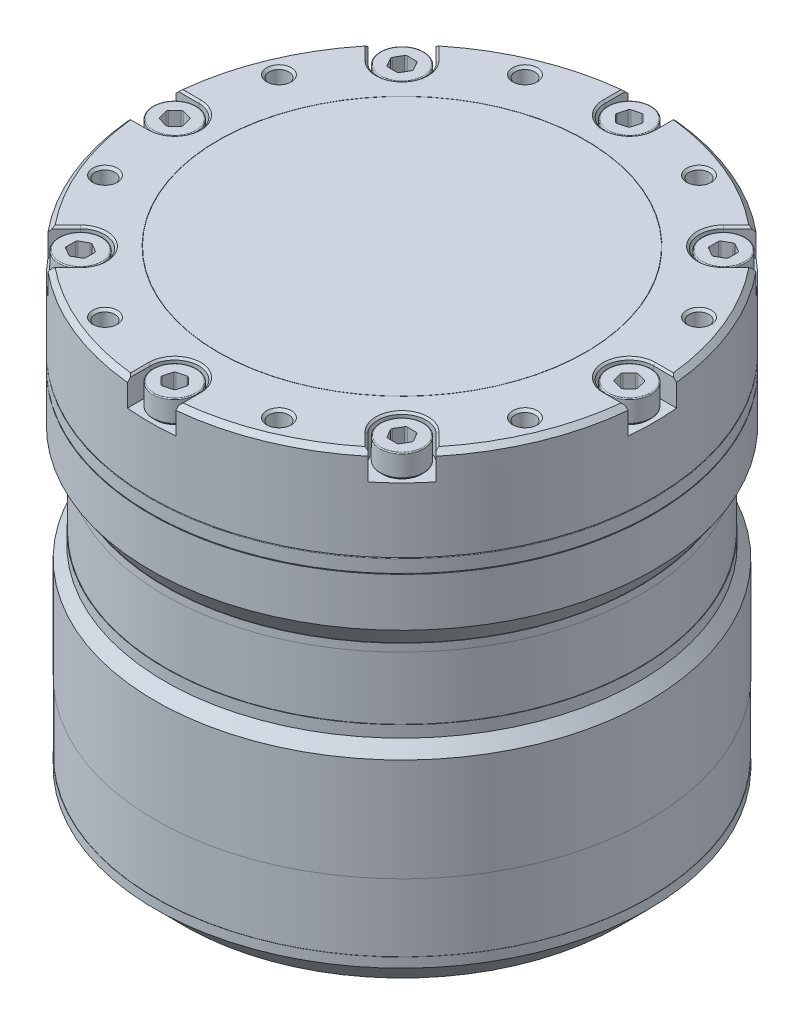
SolidWorks part; units mm, degrees
ref_plane "前视基准面" through (0, 0, 0) normal (0, 0, 1) x (1, 0, 0)
ref_plane "上视基准面" through (0, 0, 0) normal (0, 1, 0) x (1, 0, 0)
ref_plane "右视基准面" through (0, 0, 0) normal (1, 0, 0) x (0, 0, -1)
sketch "草图1" plane through (0, 0, 0) normal (0, 1, 0) x (1, 0, 0)
  circle A0 centre (0, 0) radius 26
  dimension "D1" = 52
extrude "凸台-拉伸1" add sketch "草图1" along normal blind 1.5
fillet "圆角1" radius 0.1 2 edges at (0, 0, 26) (0, 1.5, 26)
sketch "草图2" plane through (0, 1.5, 0) normal (0, 1, 0) x (1, 0, 0)
  circle A0 centre (0, 0) radius 26
  dimension "D1" = 52
extrude "凸台-拉伸2" add sketch "草图2" along normal blind 9.5
chamfer "倒角3" distance 0.5 angle 45 1 edges at (0, 11, 26)
sketch "草图4" plane through (0, 11, 0) normal (0, 1, 0) x (1, 0, 0)
  line L0 (0, 23.5) -> (0, 0) construction
  circle A0 centre (0, 23.5) radius 1.35
  dimension "D1" = 2.7
  dimension "D2" = 23.5
extrude "切除-拉伸1" cut sketch "草图4" against normal through all both and the other way through all
sketch "草图5" plane through (0, 11, 0) normal (0, 1, 0) x (1, 0, 0)
  line L0 (-2.5, 23.5) -> (-2.5, 26)
  line L1 (-2.5, 26) -> (2.5, 26)
  line L2 (2.5, 26) -> (2.5, 23.5)
  circle A0 centre (0, 23.5) radius 2.5 construction
  circle A1 centre (0, 0) radius 26 construction
  arc A2 (-2.5, 23.5) -> (2.5, 23.5) centre (0, 23.5) ccw
  dimension "D1" = 5
extrude "切除-拉伸2" cut sketch "草图5" against normal blind 2.8
chamfer "倒角1" distance 0.2 angle 45 3 edges at (-2.5, 11, -24.4386) (2.5, 11, -24.4386) (0, 11, -21)
sketch "草图6" plane through (0, 8.2, 0) normal (0, 1, 0) x (1, 0, 0)
  circle A0 centre (0, 23.5) radius 2
  dimension "D1" = 4
extrude "凸台-拉伸3" add sketch "草图6" along normal blind 0.5
sketch "草图7" plane through (0, 8.7, 0) normal (0, 1, 0) x (1, 0, 0)
  circle A0 centre (0, 23.5) radius 2.25
  dimension "D1" = 4.5
extrude "凸台-拉伸4" add sketch "草图7" along normal blind 2
chamfer "倒角2" distance 0.5 angle 45 1 edges at (0, 8.7, -21.5)
fillet "圆角2" radius 0.1 2 edges at (0, 10.7, -21.25) (0, 8.45, -21.25)
sketch "草图8" plane through (0, 10.7, 0) normal (0, 1, 0) x (1, 0, 0)
  line L1 (0.8425, 22.7904) -> (1.0865, 23.6814)
  line L2 (1.0358, 23.8748) -> (0.3862, 24.5316)
  line L3 (0.1933, 24.5844) -> (-0.7003, 24.3502)
  line L4 (-0.8425, 24.2096) -> (-1.0865, 23.3186)
  line L5 (-1.0358, 23.1252) -> (-0.3862, 22.4684)
  line L6 (-0.1933, 22.4156) -> (0.7003, 22.6498)
  circle A0 centre (0, 23.5) radius 1 construction
  arc A1 (-0.3862, 22.4684) -> (-0.1933, 22.4156) centre (-0.244, 22.609) ccw
  arc A2 (-1.0865, 23.3186) -> (-1.0358, 23.1252) centre (-0.8936, 23.2658) ccw
  arc A3 (-0.7003, 24.3502) -> (-0.8425, 24.2096) centre (-0.6496, 24.1568) ccw
  arc A4 (0.3862, 24.5316) -> (0.1933, 24.5844) centre (0.244, 24.391) ccw
  arc A5 (1.0865, 23.6814) -> (1.0358, 23.8748) centre (0.8936, 23.7342) ccw
  arc A6 (0.8425, 22.7904) -> (0.7003, 22.6498) centre (0.6496, 22.8432) cw
  dimension "D2" = 0.2
  dimension "D1" = 2
extrude "切除-拉伸3" cut sketch "草图8" against normal blind 1.8
sketch "草图9" plane through (0, 11, 0) normal (0, 1, 0) x (1, 0, 0)
  line L0 (-8.9931, 21.7112) -> (0, 0) construction
  line L1 (0, 0) -> (0, 23.5) construction
  circle A0 centre (-8.9931, 21.7112) radius 1
  dimension "D1" = 2
  dimension "D2" = 23.5
  dimension "D3" = 22.5
extrude "切除-拉伸4" cut sketch "草图9" against normal through all both and the other way through all
hole_wizard "M2.5 螺纹孔1" positions "草图10" profile "草图12" tap size "M2.5" standard "GB" end condition through all
sketch "草图10" plane through (0, 11, 0) normal (0, 1, 0) x (1, 0, 0)
  point P0 (-8.9931, 21.7112)
sketch "草图12" plane through (-8.9931, 11, -21.7112) normal (1, 0, 0) x (0, 0, 1)
  line L0 (0, 0) -> (0, 11)
  line L1 (0, 11) -> (1.025, 11)
  line L2 (1.025, 11) -> (1.025, 0.25)
  line L3 (1.025, 0.25) -> (1.275, 0)
  line L5 (1.275, 0) -> (0, 0)
  line L6 (-1.025, 0.25) -> (-1.275, 0) construction
  line L11 (0, -6.35) -> (0, 107.95) construction
  dimension "通孔螺纹孔钻头直径" = 2.05
  dimension "通孔螺纹孔钻头深度" = 11
  dimension "近端锥形沉头孔直径" = 2.55
  dimension "近端锥形沉头孔角度" = 90
cosmetic thread "孔螺蚊线1" parameters "D2"=2.5
pattern_circular "阵列(圆周)1" count 8 every 45 about axis through (0, 1.4, 0) along (0, -1, 0) of "切除-拉伸2", "切除-拉伸1", "倒角1", "凸台-拉伸3", "倒角2", "凸台-拉伸4", "圆角2", "切除-拉伸3", "切除-拉伸4", "M2.5 螺纹孔1"
cosmetic thread "孔螺蚊线2" parameters "D2"=2.5
cosmetic thread "孔螺蚊线3" parameters "D2"=2.5
cosmetic thread "孔螺蚊线4" parameters "D2"=2.5
cosmetic thread "孔螺蚊线5" parameters "D2"=2.5
cosmetic thread "孔螺蚊线6" parameters "D2"=2.5
cosmetic thread "孔螺蚊线7" parameters "D2"=2.5
cosmetic thread "孔螺蚊线8" parameters "D2"=2.5
sketch "草图13" plane through (0, 11, 0) normal (0, 1, 0) x (1, 0, 0)
  circle A0 centre (0, 0) radius 19
  circle A1 centre (0, 0) radius 18.975
  dimension "D1" = 38
  dimension "D2" = 37.95
extrude "切除-拉伸5" cut sketch "草图13" against normal blind 2
sketch "草图14" plane through (0, 0, 0) normal (0, -1, 0) x (1, 0, 0)
  circle A0 centre (0, 0) radius 26
  dimension "D1" = 52
extrude "凸台-拉伸5" add sketch "草图14" along normal blind 5
sketch "草图15" plane through (0, 0, 0) normal (0, 0, 1) x (1, 0, 0)
  line L0 (0, 0) -> (0, 35.6322) construction
  line L1 (26, -5) -> (24.45, -7.2136)
  line L2 (-26, -5) -> (26, -5) construction
  line L3 (24.45, -7.2136) -> (0, -7.2136)
  line L4 (26, -5) -> (0, -5)
  line L5 (0, -5) -> (0, -7.2136)
  dimension "D1" = 55
  dimension "D2" = 24.45
revolve "旋转1" add sketch "草图15" angle 360 about L0
sketch "草图17" plane through (0, -7.2136, 0) normal (0, -1, 0) x (1, 0, 0)
  circle A0 centre (0, 0) radius 24.5
  dimension "D1" = 49
extrude "凸台-拉伸6" add sketch "草图17" along normal blind 0.8
sketch "草图18" plane through (0, -8.0136, 0) normal (0, -1, 0) x (1, 0, 0)
  circle A0 centre (0, 0) radius 24.45
  dimension "D1" = 48.9
extrude "凸台-拉伸7" add sketch "草图18" along normal blind 6.5
sketch "草图19" plane through (0, -14.5136, 0) normal (0, -1, 0) x (1, 0, 0)
  circle A0 centre (0, 0) radius 24.5
  dimension "D1" = 49
extrude "凸台-拉伸8" add sketch "草图19" along normal blind 1.2
sketch "草图20" plane through (0, 0, 0) normal (0, 0, 1) x (1, 0, 0)
  line L0 (0, 0) -> (0, -33.6201) construction
  line L1 (0, -15.2179) -> (24.45, -15.7136)
  line L2 (-24.5, -15.7136) -> (24.5, -15.7136) construction
  line L3 (24.45, -15.7136) -> (25.5, -16.965)
  line L4 (25.5, -16.965) -> (0, -16.965)
  line L5 (0, -16.965) -> (0, -15.2179)
  dimension "D1" = 24.45
  dimension "D2" = 25.5
  dimension "D3" = 50
revolve "旋转2" add sketch "草图20" angle 360 about L0
sketch "草图21" plane through (0, -16.965, 0) normal (0, -1, 0) x (1, 0, 0)
  circle A1 centre (0, 0) radius 25.5
  circle A2 centre (0, 0) radius 25.5
  dimension "D1" = 0
extrude "凸台-拉伸9" add sketch "草图21" along normal blind 10.64
sketch "草图22" plane through (0, -27.605, 0) normal (0, -1, 0) x (1, 0, 0)
  circle A1 centre (0, 0) radius 25.475
  dimension "D1" = 50.95
extrude "凸台-拉伸10" add sketch "草图22" along normal blind 7
sketch "草图23" plane through (0, -34.605, 0) normal (0, -1, 0) x (1, 0, 0)
  circle A0 centre (0, 0) radius 25.5
  dimension "D1" = 51
extrude "凸台-拉伸11" add sketch "草图23" along normal blind 4
chamfer "倒角4" distance 3 angle 45 1 edges at (25.5, -38.605, 0)
